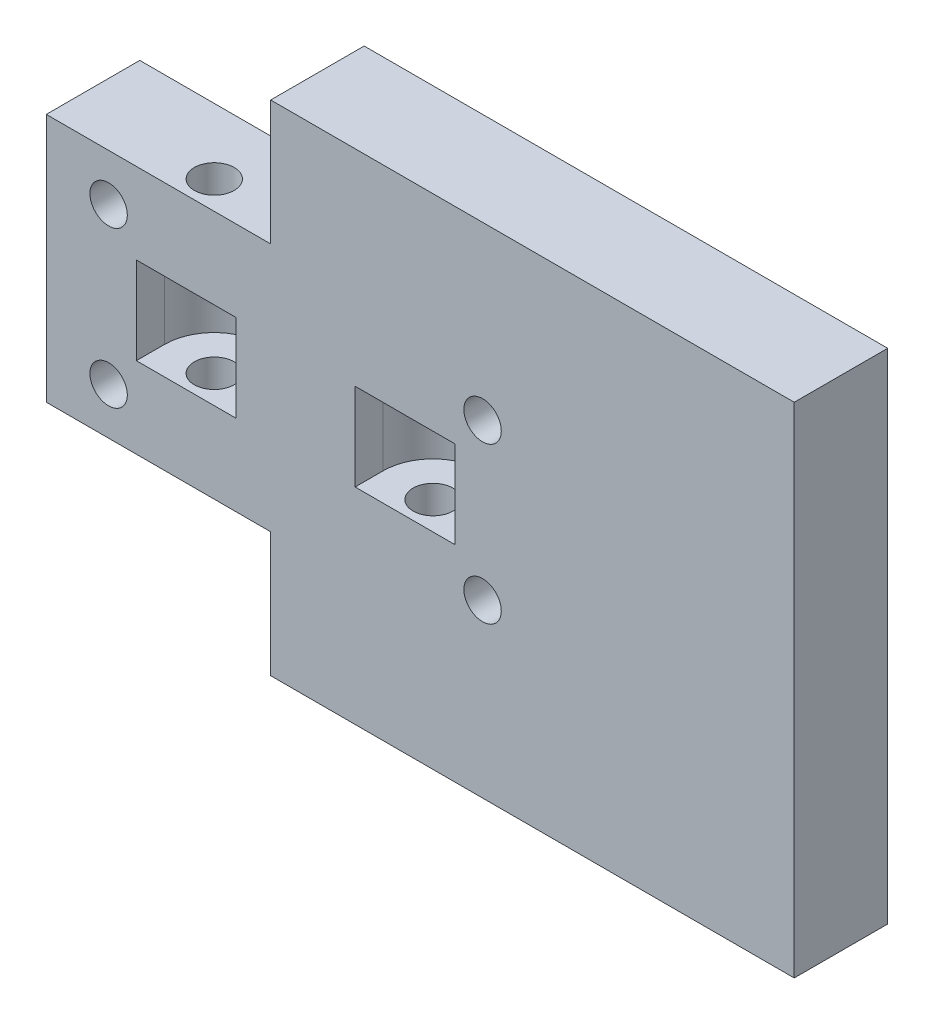
SolidWorks part; units mm, degrees
ref_plane "Front Plane" through (0, 0, 0) normal (0, 0, 1) x (1, 0, 0)
ref_plane "Top Plane" through (0, 0, 0) normal (0, 1, 0) x (1, 0, 0)
ref_plane "Right Plane" through (0, 0, 0) normal (1, 0, 0) x (0, 0, -1)
sketch "Sketch1" plane through (0, 0, 0) normal (0, 0, 1) x (1, 0, 0)
  line L2 (-38.1, -12.7) -> (-38.1, 12.7)
  line L3 (-38.1, 12.7) -> (38.1, 12.7)
  line L10 (38.1, -12.7) -> (38.1, 12.7)
  line L11 (-38.1, -12.7) -> (38.1, -12.7)
  line L14 (-38.1, 12.7) -> (38.1, -12.7) construction
  point P2 (0, 0)
  dimension "D1" = 76.2
  dimension "D2" = 25.4
extrude "Boss-Extrude1" add sketch "Sketch1" along normal blind 9.525
sketch "Sketch6" plane through (0, 0, 9.525) normal (0, 0, -1) x (-1, 0, 0)
  line L7 (-38.1, 25.4) -> (-38.1, -25.4)
  line L17 (15.24, 25.4) -> (15.24, -25.4)
  line L18 (15.24, -25.4) -> (-38.1, -25.4)
  line L20 (-38.1, -12.7) -> (-38.1, 12.7) construction
  line L22 (15.24, 25.4) -> (-38.1, 25.4)
  point P1 (-38.1, 0)
  dimension "D1" = 50.8
  dimension "D4" = 53.34
extrude "Boss-Extrude2" add sketch "Sketch6" along normal up to surface (9.525 mm away) up to face at (0, 0, 0)
sketch "Sketch4" plane through (0, 0, 0) normal (0, 1, 0) x (1, 0, 0)
  line L7 (-15.24, -9.525) -> (-38.1, -9.525) construction
  line L8 (-28.9242, -6.6675) -> (-28.9242, -9.525)
  line L9 (-18.7643, -6.6675) -> (-18.7642, -9.525)
  line L10 (-18.7642, -9.525) -> (-28.9242, -9.525)
  line L11 (-38.1, -9.525) -> (-38.1, 0) construction
  arc A2 (-18.7643, -6.6675) -> (-28.9242, -6.6675) centre (-23.8442, -6.6675) ccw
  dimension "D1" = 10.16
  dimension "D2" = 2.8575
  dimension "D3" = 14.2558
extrude "Cut-Extrude2" cut sketch "Sketch4" against normal mid plane 8.89
ref_plane "Plane3" through (-12.7, 0, 0) normal (-1, 0, 0) x (0, 0, 1)
sketch "Sketch2" plane through (0, 0, 9.525) normal (0, 0, 1) x (1, 0, 0)
  line L0 (-38.1, -12.7) -> (-15.24, -12.7) construction
  line L1 (-38.1, 12.7) -> (-38.1, -12.7) construction
  circle A0 centre (-31.75, 7.9375) radius 1.905
  dimension "D1" = 3.81
  dimension "D2" = 20.6375
  dimension "D3" = 6.35
extrude "Cut-Extrude1" cut sketch "Sketch2" against normal up to surface (9.525 mm away) up to face at (-7.62, 0, 0)
sketch "Sketch5" plane through (0, 12.7, 0) normal (0, 1, 0) x (1, 0, 0)
  line L0 (-15.24, -9.525) -> (-38.1, -9.525) construction
  line L1 (-38.1, -9.525) -> (-38.1, 0) construction
  circle A0 centre (-23.8442, -6.6675) radius 2.032
  dimension "D3" = 4.064
  dimension "D1" = 2.8575
  dimension "D2" = 14.2558
extrude "Cut-Extrude3" cut sketch "Sketch5" along normal blind 3.175 and the other way through all
mirror "Mirror1" about plane through (0, 0, 0) normal (0, 1, 0) of "Cut-Extrude1"
mirror "Mirror2" about plane through (-12.7, 0, 0) normal (-1, 0, 0) of "Mirror1", "Cut-Extrude3", "Cut-Extrude2"
